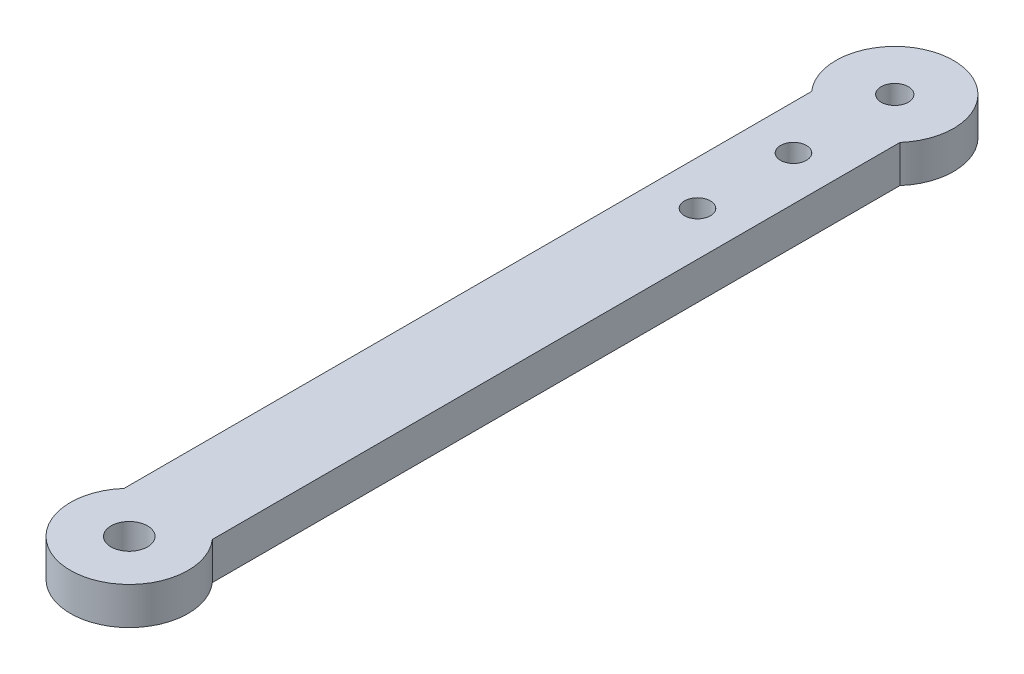
SolidWorks part; units mm, degrees
ref_plane "Front Plane" through (0, 0, 0) normal (0, 0, 1) x (1, 0, 0)
ref_plane "Top Plane" through (0, 0, 0) normal (0, 1, 0) x (1, 0, 0)
ref_plane "Right Plane" through (0, 0, 0) normal (1, 0, 0) x (0, 0, -1)
sketch "Sketch1" plane through (0, 0, 0) normal (0, 1, 0) x (1, 0, 0)
  line L1 (-3.75, -61.6928) -> (-3.75, -3.3072)
  line L4 (3.75, -61.6928) -> (3.75, -3.3072)
  line L5 (-3.75, -3.3072) -> (0, 0) construction
  line L6 (0, 0) -> (3.75, -3.3072) construction
  line L7 (-3.75, -3.3072) -> (3.75, -3.3072) construction
  arc A1 (3.75, -3.3072) -> (-3.75, -3.3072) centre (0, 0) ccw
  arc A2 (-3.75, -61.6928) -> (3.75, -61.6928) centre (0, -65) ccw
  circle A3 centre (0, -65) radius 1.55
  circle A5 centre (0, -8.6) radius 1.1
  circle A6 centre (0, -16.75) radius 1.1
  circle A25 centre (0, 0) radius 1.15
  dimension "D2" = 2.2
  dimension "D3" = 10
  dimension "D6" = 10
  dimension "D5" = 3.1
  dimension "D8" = 2.3
  dimension "D1" = 8.15
  dimension "D4" = 7.5
  dimension "D7" = 65
  dimension "D9" = 8.6
extrude "Boss-Extrude1" add sketch "Sketch1" along normal blind 3.175
